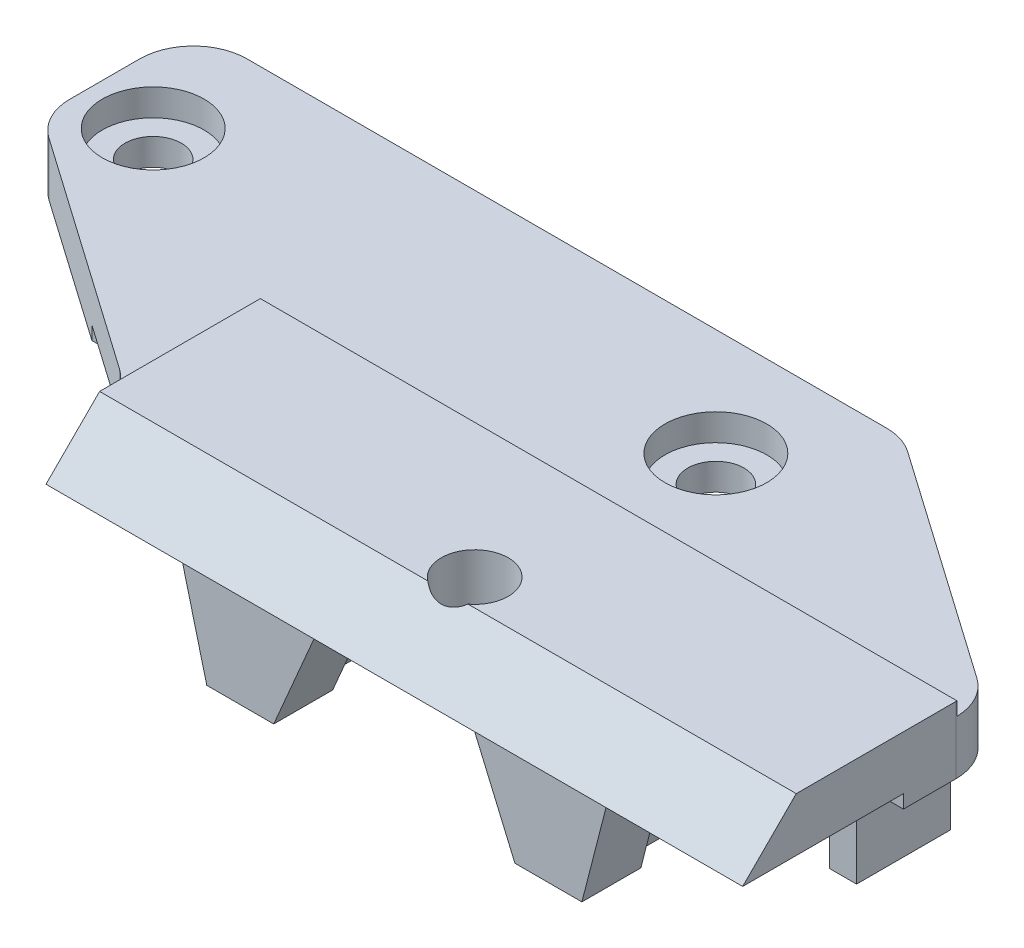
SolidWorks part; units mm, degrees
material "ABS"
ref_plane "正面" through (0, 0, 0) normal (0, 0, 1) x (1, 0, 0)
ref_plane "平面" through (0, 0, 0) normal (0, 1, 0) x (1, 0, 0)
ref_plane "右側面" through (0, 0, 0) normal (1, 0, 0) x (0, 0, -1)
sketch "ｽｹｯﾁ1" plane through (0, 0, 0) normal (0, 1, 0) x (1, 0, 0)
  line L0 (-13, 8) -> (3, 8)
  line L2 (-13, -5) -> (-13, -8)
  line L3 (-13, -8) -> (13, -8)
  line L4 (13, 1) -> (13, -8)
  line L5 (-13, 8) -> (13, -8) construction
  line L6 (-13, -8) -> (13, 8) construction
  line L7 (-13, -5) -> (-23.5, 2.35)
  line L8 (-23.5, 2.35) -> (-23.5, 8)
  line L9 (-23.5, 8) -> (-13, 8)
  line L10 (3, 8) -> (13, 1)
  point P7 (0, 0)
  dimension "D1" = 0
  dimension "D2" = 0
  dimension "D4" = 16
  dimension "D5" = 3
  dimension "D3" = 26
  dimension "D6" = 9
  dimension "D7" = 16
  dimension "D8" = 3
  dimension "D9" = 8
  dimension "D10" = 13
  dimension "D11" = 36.5
extrude "ﾎﾞｽ - 押し出し1" add sketch "ｽｹｯﾁ1" along normal blind 2
sketch "ｽｹｯﾁ4" plane through (0, 0, 8) normal (0, 0, 1) x (1, 0, 0)
  line L1 (-7, -3.5) -> (-4.5, -3.5)
  line L2 (-4.5, -3.5) -> (-3, 0)
  line L4 (3, 0) -> (4.5, -3.5)
  line L5 (4.5, -3.5) -> (7, -3.5)
  line L8 (7, -3.5) -> (7.9, 0)
  line L10 (-7, -3.5) -> (-7.9, 0)
  line L12 (3, 0) -> (0, 0) construction
  line L13 (0, 0) -> (-3, 0) construction
  line L14 (-7.9, 0) -> (-3, 0)
  line L15 (3, 0) -> (7.9, 0)
  line L16 (-13, 0) -> (13, 0) construction
  dimension "D1" = 7.9
  dimension "D2" = 0
  dimension "D3" = 3
  dimension "D4" = 7
  dimension "D5" = 2.5
  dimension "D9" = 3.5
extrude "ﾎﾞｽ - 押し出し3" add sketch "ｽｹｯﾁ4" against normal blind 6
sketch "ｽｹｯﾁ5" plane through (0, 2, 0) normal (0, 1, 0) x (1, 0, 0)
  line L1 (-13, -8) -> (13, -8) construction
  circle A0 centre (0, -5) radius 1.25
  dimension "D1" = 2.5
  dimension "D2" = 1.25
  dimension "D3" = 3
  dimension "D4" = 0
extrude "ｶｯﾄ - 押し出し1" cut sketch "ｽｹｯﾁ5" against normal up to next
fillet "ﾌｨﾚｯﾄ1" [suppressed] radius 2
sketch "ｽｹｯﾁ6" plane through (13, 0, 0) normal (1, 0, 0) x (0, 0, -1)
  line L0 (8, 2) -> (8, 0) construction
  line L1 (-2, 0) -> (8, 0)
  line L2 (-2, 0) -> (-2, -0.5)
  line L3 (-2, -0.5) -> (8, -0.5)
  line L4 (8, 0) -> (8, -0.5)
  line L5 (-2, 0) -> (8, -0.5) construction
  line L6 (-2, -0.5) -> (8, 0) construction
  point P4 (3, -0.25)
  dimension "D1" = 0.5
extrude "ﾎﾞｽ - 押し出し4" add sketch "ｽｹｯﾁ6" against normal up to surface (36.5 mm away) up to face at (-23.5, 1, -5.175)
sketch "ｽｹｯﾁ7" plane through (13, 0, 0) normal (1, 0, 0) x (0, 0, -1)
  line L0 (-8, 2) -> (1, 2) construction
  line L1 (0, 2) -> (8, 2)
  line L2 (0, 2) -> (0, 1.5)
  line L3 (0, 1.5) -> (8, 1.5)
  line L4 (8, 2) -> (8, 1.5)
  line L5 (0, 2) -> (8, 1.5) construction
  line L6 (0, 1.5) -> (8, 2) construction
  line L7 (8, 0) -> (8, -0.5) construction
  point P4 (4, 1.75)
  dimension "D1" = 0.5
  dimension "D2" = 8
extrude "ｶｯﾄ - 押し出し2" cut sketch "ｽｹｯﾁ7" against normal up to next
sketch "ｽｹｯﾁ10" plane through (0, -0.5, 0) normal (0, -1, 0) x (1, 0, 0)
  line L0 (7.7714, 2) -> (13, 2) construction
  line L1 (10.25, 2) -> (11.25, 2)
  line L2 (10.25, 2) -> (10.25, -1.5)
  line L3 (10.25, -1.5) -> (11.25, -1.5)
  line L4 (11.25, 2) -> (11.25, -1.5)
  line L5 (10.25, 2) -> (11.25, -1.5) construction
  line L6 (10.25, -1.5) -> (11.25, 2) construction
  line L7 (-23.5, -8) -> (13, -8) construction
  line L8 (13, 2) -> (13, -8) construction
  point P4 (10.75, 0.25)
  dimension "D1" = 6.5
  dimension "D2" = 1.75
  dimension "D3" = 1
extrude "ﾎﾞｽ - 押し出し5" add sketch "ｽｹｯﾁ10" along normal blind 3.3
mirror "ﾐﾗｰ1" about plane through (0, 0, 0) normal (1, 0, 0) of "ﾎﾞｽ - 押し出し5"
chamfer "面取り1" distance 2 angle 45 1 edges at (0, 2, 8)
sketch "ｽｹｯﾁ12" plane through (0, 0, 0) normal (0, 1, 0) x (1, 0, 0)
  line L0 (3, 8) -> (13, 8)
  line L1 (13, 8) -> (13, 1)
  line L2 (13, 1) -> (3, 8)
  line L3 (-23.5, -2) -> (-17.2857, -2)
  line L4 (-17.2857, -2) -> (-23.5, 2.35)
  line L5 (-23.5, 2.35) -> (-23.5, -2)
extrude "ｶｯﾄ - 押し出し3" cut sketch "ｽｹｯﾁ12" against normal up to next
sketch "ｽｹｯﾁ13" plane through (0, 2, 0) normal (0, 1, 0) x (1, 0, 0)
  line L0 (-13, -5) -> (-13, 0)
  line L1 (-20.1429, 0) -> (13, 0) construction
  line L2 (-13, 0) -> (-20.1429, 0)
  line L3 (-20.1429, 0) -> (-13, -5)
extrude "ｶｯﾄ - 押し出し4" cut sketch "ｽｹｯﾁ13" against normal up to surface (0.5 mm away) up to face at (-6.3571, 1.5, -3.225)
hole_wizard "M2 丸平ねじ用座ぐり穴2" positions "ｽｹｯﾁ14" profile "ｽｹｯﾁ15" counterbore size "M2" standard "JIS" end condition through all
sketch "ｽｹｯﾁ14" plane through (0, 1.5, 0) normal (0, 1, 0) x (1, 0, 0)
  line L0 (-21, 4) -> (0, 4) construction
  line L2 (-23.5, 8) -> (3, 8) construction
  arc A0 (0.75, -6) -> (-0.75, -6) centre (0, -5) ccw construction
  point P0 (-21, 4)
  point P2 (0, 4)
  dimension "D1" = 4
  dimension "D2" = 21
  dimension "D3" = 0
sketch "ｽｹｯﾁ15" plane through (-21, 1.5, -4) normal (1, 0, 0) x (0, 0, 1)
  line L0 (0, 0) -> (0, 5.3)
  line L1 (0, 5.3) -> (1.05, 5.3)
  line L3 (1.05, 5.3) -> (1.05, 1)
  line L4 (1.05, 1) -> (1.9, 1)
  line L5 (1.9, 1) -> (1.9, 0)
  line L7 (1.9, 0) -> (0, 0)
  line L11 (0, -6.35) -> (0, 107.95) construction
  dimension "通し穴の直径" = 2.1
  dimension "通し穴の深さ" = 5.3
  dimension "座ぐり穴の直径" = 3.8
  dimension "座ぐり穴の深さ" = 1
fillet "ﾌｨﾚｯﾄ3" radius 2 5 edges at (-13, 0.75, 5) (13, 0.5, -1) (3, 0.5, -8) (-23.5, 0.5, -8) (-23.5, 0.5, -2.35)
ref_plane "平面1" through (0, 0, 5) normal (0, 0, 1) x (1, 0, 0)
sketch "ｽｹｯﾁ16" plane through (0, 0, 5) normal (0, 0, 1) x (1, 0, 0)
  line L0 (-7.9, 0) -> (-7, -3.5)
  line L1 (-7, -3.5) -> (-6.4, -3.5)
  line L2 (-7, -3.5) -> (-4.5, -3.5) construction
  line L3 (-6.4, -3.5) -> (-7.3, 0)
  line L4 (-3, 0) -> (-7.9, 0) construction
  line L5 (-7.3, 0) -> (-7.9, 0)
  line L6 (-3, 0) -> (-4.5, -3.5)
  line L7 (-4.5, -3.5) -> (-5.1, -3.5)
  line L8 (-5.1, -3.5) -> (-3.6, 0)
  line L9 (-3.6, 0) -> (-3, 0)
  line L10 (3, 0) -> (4.5, -3.5)
  line L11 (4.5, -3.5) -> (5.1, -3.5)
  line L12 (4.5, -3.5) -> (7, -3.5) construction
  line L13 (5.1, -3.5) -> (3.6, 0)
  line L14 (7.9, 0) -> (3, 0) construction
  line L15 (3.6, 0) -> (3, 0)
  line L16 (7.9, 0) -> (7, -3.5)
  line L17 (7, -3.5) -> (6.4, -3.5)
  line L18 (6.4, -3.5) -> (7.3, 0)
  line L19 (7.3, 0) -> (7.9, 0)
  dimension "D1" = 0.6
  dimension "D2" = 0.6
  dimension "D3" = 0.6
  dimension "D4" = 0.6
extrude "ｶｯﾄ - 押し出し5" cut sketch "ｽｹｯﾁ16" against normal mid plane 1.6
